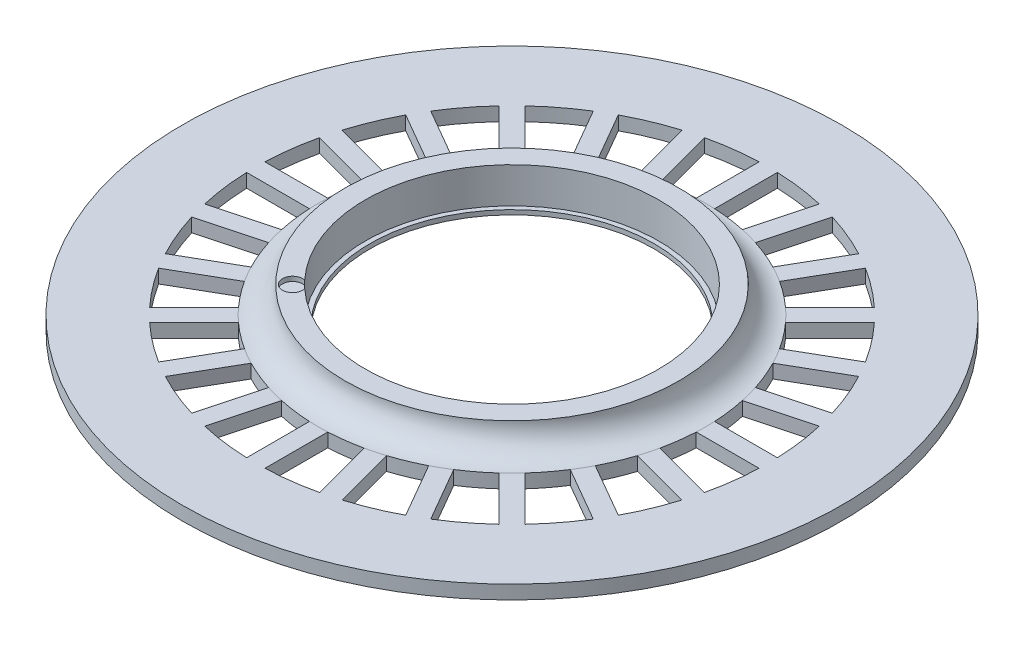
SolidWorks part; units mm, degrees
ref_plane "Front Plane" through (0, 0, 0) normal (0, 0, 1) x (1, 0, 0)
ref_plane "Top Plane" through (0, 0, 0) normal (0, 1, 0) x (1, 0, 0)
ref_plane "Right Plane" through (0, 0, 0) normal (1, 0, 0) x (0, 0, -1)
sketch "Sketch1" plane through (0, 0, 0) normal (0, 1, 0) x (1, 0, 0)
  circle A0 centre (0, 0) radius 16.025
  circle A1 centre (0, 0) radius 36
  dimension "D1" = 32.05
  dimension "D2" = 72
extrude "Boss-Extrude1" add sketch "Sketch1" along normal blind 1
sketch "Sketch2" plane through (0, 0, 0) normal (0, -1, 0) x (1, 0, 0)
  circle A0 centre (0, 0) radius 16.95 construction
  circle A1 centre (0, 0) radius 18.25 construction
  circle A2 centre (0, 0) radius 18.25
  circle A3 centre (0, 0) radius 16.025 construction
  circle A4 centre (0, 0) radius 16.025
  point P3 (-11.9855, 11.9855)
extrude "Boss-Extrude2" add sketch "Sketch2" against normal offset from surface (3.9 mm away) 3.9 up to face at (0, 0, 36)
fillet "Fillet1" radius 2.9 1 edges at (0, 1, 18.25)
sketch "Sketch4" plane through (0, 0, 0) normal (0, 1, 0) x (1, 0, 0)
  circle A0 centre (0, 0) radius 15.525
  circle A1 centre (0, 0) radius 36
  circle A2 centre (0, 0) radius 36
  circle A3 centre (0, 0) radius 16.025 construction
  dimension "D2" = 0.5
  dimension "D1" = 0
extrude "Boss-Extrude3" add sketch "Sketch4" against normal blind 0.5
sketch "Sketch5" plane through (0, 1, 0) normal (0, 1, 0) x (1, 0, 0)
  line L0 (27.99, -0.75) -> (19.9859, -0.75) construction
  line L1 (19.9859, 0.75) -> (27.99, 0.75) construction
  line L2 (27.99, -0.75) -> (19.9859, -0.75) construction
  line L3 (19.9859, 0.75) -> (27.99, 0.75) construction
  line L4 (0, 0) -> (36, 0) construction
  line L5 (0, 0) -> (34.7733, 9.3175) construction
  line L6 (34.7733, 9.3175) -> (36, 0) construction
  line L7 (0, 0) -> (35.3867, 4.6587) construction
  line L8 (27.99, 1) -> (21.1263, 1)
  line L9 (27.295, 6.2784) -> (20.6653, 4.502)
  line L10 (27.99, -1) -> (21.1263, -1)
  line L11 (27.295, -6.2784) -> (20.6653, -4.502)
  line L12 (26.7774, -8.2103) -> (20.1477, -6.4338)
  line L13 (24.74, -13.129) -> (18.796, -9.6971)
  line L14 (23.74, -14.861) -> (17.796, -11.4292)
  line L15 (20.499, -19.0848) -> (15.6457, -14.2315)
  line L16 (19.0848, -20.499) -> (14.2315, -15.6457)
  line L17 (14.861, -23.74) -> (11.4292, -17.796)
  line L18 (13.129, -24.74) -> (9.6971, -18.796)
  line L19 (8.2103, -26.7774) -> (6.4338, -20.1477)
  line L20 (6.2784, -27.295) -> (4.502, -20.6653)
  line L21 (1, -27.99) -> (1, -21.1263)
  line L22 (-1, -27.99) -> (-1, -21.1263)
  line L23 (-6.2784, -27.295) -> (-4.502, -20.6653)
  line L24 (-8.2103, -26.7774) -> (-6.4338, -20.1477)
  line L25 (-13.129, -24.74) -> (-9.6971, -18.796)
  line L26 (-14.861, -23.74) -> (-11.4292, -17.796)
  line L27 (-19.0848, -20.499) -> (-14.2315, -15.6457)
  line L28 (-20.499, -19.0848) -> (-15.6457, -14.2315)
  line L29 (-23.74, -14.861) -> (-17.796, -11.4292)
  line L30 (-24.74, -13.129) -> (-18.796, -9.6971)
  line L31 (-26.7774, -8.2103) -> (-20.1477, -6.4338)
  line L32 (-27.295, -6.2784) -> (-20.6653, -4.502)
  line L33 (-27.99, -1) -> (-21.1263, -1)
  line L34 (-27.99, 1) -> (-21.1263, 1)
  line L35 (-27.295, 6.2784) -> (-20.6653, 4.502)
  line L36 (-26.7774, 8.2103) -> (-20.1477, 6.4338)
  line L37 (-24.74, 13.129) -> (-18.796, 9.6971)
  line L38 (-23.74, 14.861) -> (-17.796, 11.4292)
  line L39 (-20.499, 19.0848) -> (-15.6457, 14.2315)
  line L40 (-19.0848, 20.499) -> (-14.2315, 15.6457)
  line L41 (-14.861, 23.74) -> (-11.4292, 17.796)
  line L42 (-13.129, 24.74) -> (-9.6971, 18.796)
  line L43 (-8.2103, 26.7774) -> (-6.4338, 20.1477)
  line L44 (-6.2784, 27.295) -> (-4.502, 20.6653)
  line L45 (-1, 27.99) -> (-1, 21.1263)
  line L46 (1, 27.99) -> (1, 21.1263)
  line L47 (6.2784, 27.295) -> (4.502, 20.6653)
  line L48 (8.2103, 26.7774) -> (6.4338, 20.1477)
  line L49 (13.129, 24.74) -> (9.6971, 18.796)
  line L50 (14.861, 23.74) -> (11.4292, 17.796)
  line L51 (19.0848, 20.499) -> (14.2315, 15.6457)
  line L52 (20.499, 19.0848) -> (15.6457, 14.2315)
  line L53 (23.74, 14.861) -> (17.796, 11.4292)
  line L54 (24.74, 13.129) -> (18.796, 9.6971)
  line L55 (26.7774, 8.2103) -> (20.1477, 6.4338)
  line L56 (0, 0) -> (21.1263, 1) construction
  circle A0 centre (0, 0) radius 21.15 construction
  circle A2 centre (0, 0) radius 36 construction
  arc A3 (21.1263, 1) -> (20.6653, 4.502) centre (0, 0) ccw
  arc A4 (27.99, 1) -> (27.295, 6.2784) centre (0, 0) ccw
  arc A5 (27.295, -6.2784) -> (27.99, -1) centre (0, 0) ccw
  arc A6 (20.6653, -4.502) -> (21.1263, -1) centre (0, 0) ccw
  arc A7 (24.74, -13.129) -> (26.7774, -8.2103) centre (0, 0) ccw
  arc A8 (18.796, -9.6971) -> (20.1477, -6.4338) centre (0, 0) ccw
  arc A9 (20.499, -19.0848) -> (23.74, -14.861) centre (0, 0) ccw
  arc A10 (15.6457, -14.2315) -> (17.796, -11.4292) centre (0, 0) ccw
  arc A11 (14.861, -23.74) -> (19.0848, -20.499) centre (0, 0) ccw
  arc A12 (11.4292, -17.796) -> (14.2315, -15.6457) centre (0, 0) ccw
  arc A13 (8.2103, -26.7774) -> (13.129, -24.74) centre (0, 0) ccw
  arc A14 (6.4338, -20.1477) -> (9.6971, -18.796) centre (0, 0) ccw
  arc A15 (1, -27.99) -> (6.2784, -27.295) centre (0, 0) ccw
  arc A16 (1, -21.1263) -> (4.502, -20.6653) centre (0, 0) ccw
  arc A17 (-6.2784, -27.295) -> (-1, -27.99) centre (0, 0) ccw
  arc A18 (-4.502, -20.6653) -> (-1, -21.1263) centre (0, 0) ccw
  arc A19 (-13.129, -24.74) -> (-8.2103, -26.7774) centre (0, 0) ccw
  arc A20 (-9.6971, -18.796) -> (-6.4338, -20.1477) centre (0, 0) ccw
  arc A21 (-19.0848, -20.499) -> (-14.861, -23.74) centre (0, 0) ccw
  arc A22 (-14.2315, -15.6457) -> (-11.4292, -17.796) centre (0, 0) ccw
  arc A23 (-23.74, -14.861) -> (-20.499, -19.0848) centre (0, 0) ccw
  arc A24 (-17.796, -11.4292) -> (-15.6457, -14.2315) centre (0, 0) ccw
  arc A25 (-26.7774, -8.2103) -> (-24.74, -13.129) centre (0, 0) ccw
  arc A26 (-20.1477, -6.4338) -> (-18.796, -9.6971) centre (0, 0) ccw
  arc A27 (-27.99, -1) -> (-27.295, -6.2784) centre (0, 0) ccw
  arc A28 (-21.1263, -1) -> (-20.6653, -4.502) centre (0, 0) ccw
  arc A29 (-27.295, 6.2784) -> (-27.99, 1) centre (0, 0) ccw
  arc A30 (-20.6653, 4.502) -> (-21.1263, 1) centre (0, 0) ccw
  arc A31 (-24.74, 13.129) -> (-26.7774, 8.2103) centre (0, 0) ccw
  arc A32 (-18.796, 9.6971) -> (-20.1477, 6.4338) centre (0, 0) ccw
  arc A33 (-20.499, 19.0848) -> (-23.74, 14.861) centre (0, 0) ccw
  arc A34 (-15.6457, 14.2315) -> (-17.796, 11.4292) centre (0, 0) ccw
  arc A35 (-14.861, 23.74) -> (-19.0848, 20.499) centre (0, 0) ccw
  arc A36 (-11.4292, 17.796) -> (-14.2315, 15.6457) centre (0, 0) ccw
  arc A37 (-8.2103, 26.7774) -> (-13.129, 24.74) centre (0, 0) ccw
  arc A38 (-6.4338, 20.1477) -> (-9.6971, 18.796) centre (0, 0) ccw
  arc A39 (-1, 27.99) -> (-6.2784, 27.295) centre (0, 0) ccw
  arc A40 (-1, 21.1263) -> (-4.502, 20.6653) centre (0, 0) ccw
  arc A41 (6.2784, 27.295) -> (1, 27.99) centre (0, 0) ccw
  arc A42 (4.502, 20.6653) -> (1, 21.1263) centre (0, 0) ccw
  arc A43 (13.129, 24.74) -> (8.2103, 26.7774) centre (0, 0) ccw
  arc A44 (9.6971, 18.796) -> (6.4338, 20.1477) centre (0, 0) ccw
  arc A45 (19.0848, 20.499) -> (14.861, 23.74) centre (0, 0) ccw
  arc A46 (14.2315, 15.6457) -> (11.4292, 17.796) centre (0, 0) ccw
  arc A47 (23.74, 14.861) -> (20.499, 19.0848) centre (0, 0) ccw
  arc A48 (17.796, 11.4292) -> (15.6457, 14.2315) centre (0, 0) ccw
  arc A49 (26.7774, 8.2103) -> (24.74, 13.129) centre (0, 0) ccw
  arc A50 (20.1477, 6.4338) -> (18.796, 9.6971) centre (0, 0) ccw
  dimension "D1" = 15
  dimension "D2" = 1
  dimension "D4" = 21.15
  dimension "D3" = 24
extrude "Cut-Extrude1" cut sketch "Sketch5" against normal through all
sketch "Sketch7" plane through (0, 3.9, 0) normal (0, 1, 0) x (1, 0, 0)
  line L0 (0, 0) -> (-11.9855, -11.9855) construction
  circle A0 centre (-11.9855, -11.9855) radius 1.1
  dimension "D1" = 2.2
extrude "Cut-Extrude2" cut sketch "Sketch7" against normal blind 0.5
